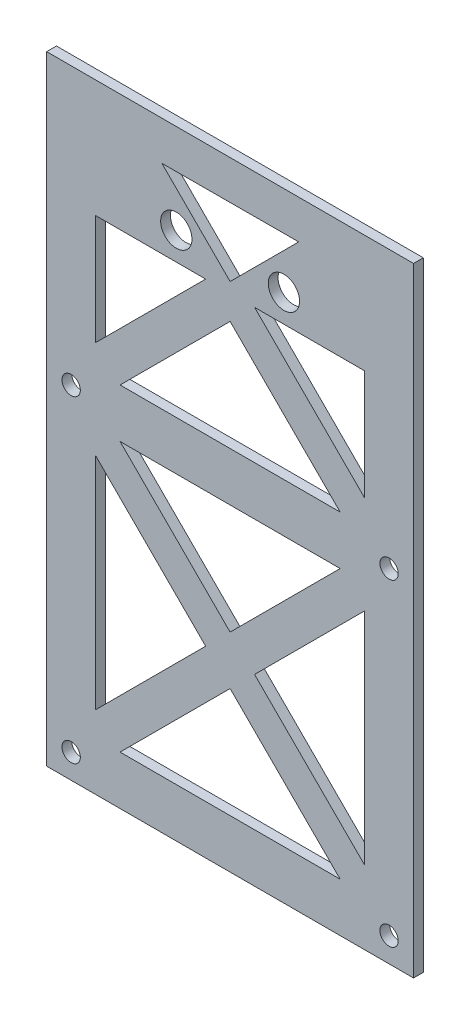
SolidWorks part; units mm, degrees
ref_plane "Front Plane" through (0, 0, 0) normal (0, 0, 1) x (1, 0, 0)
ref_plane "Top Plane" through (0, 0, 0) normal (0, 1, 0) x (1, 0, 0)
ref_plane "Right Plane" through (0, 0, 0) normal (1, 0, 0) x (0, 0, -1)
sketch "Sketch1" plane through (0, 0, 0) normal (0, 0, 1) x (1, 0, 0)
  line L2 (-37.5, -138.0294) -> (37.5, -138.0294)
  line L3 (5, -162.0484) -> (27.5, -162.0484)
  line L6 (-37.5, -264.5484) -> (37.5, -264.5484)
  line L7 (-27.5, -204.5484) -> (-27.5, -249.5484)
  line L8 (37.5, -264.5484) -> (37.5, -138.0294)
  line L9 (-37.5, -264.5484) -> (-37.5, -138.0294)
  line L11 (-22.5, -254.5484) -> (22.5, -254.5484)
  line L12 (27.5, -249.5484) -> (27.5, -204.5484)
  line L13 (-5, -162.0484) -> (-27.5, -162.0484)
  line L14 (-22.5, -199.5484) -> (22.5, -199.5484)
  line L15 (-27.5, -184.5484) -> (-27.5, -162.0484)
  line L17 (27.5, -184.5484) -> (27.5, -162.0484)
  line L19 (-27.5, -249.5484) -> (-5, -227.0484)
  line L20 (27.5, -204.5484) -> (5, -227.0484)
  line L21 (-27.5, -204.5484) -> (-5, -227.0484)
  line L22 (-22.5, -199.5484) -> (0, -222.0484)
  line L23 (0, -222.0484) -> (22.5, -199.5484)
  line L24 (0, -232.0484) -> (22.5, -254.5484)
  line L25 (5, -227.0484) -> (27.5, -249.5484)
  line L26 (-22.5, -189.5484) -> (22.5, -189.5484)
  line L27 (0, -232.0484) -> (-22.5, -254.5484)
  line L31 (-27.5, -184.5484) -> (-5, -162.0484)
  line L32 (0, -167.0484) -> (22.5, -189.5484)
  line L33 (5, -162.0484) -> (27.5, -184.5484)
  line L34 (0, -167.0484) -> (-22.5, -189.5484)
  line L35 (14.0243, -145.954) -> (0, -159.9784)
  line L37 (0, -159.9784) -> (-13.9583, -146.0201)
  line L38 (-13.9583, -146.0201) -> (14.0243, -145.954)
  circle A0 centre (32.5, -259.5484) radius 1.875
  circle A1 centre (-32.5, -259.5484) radius 1.875
  circle A2 centre (-32.5, -194.5484) radius 1.875
  circle A3 centre (32.5, -194.5484) radius 1.875
  circle A4 centre (11, -156.3894) radius 3.2
  circle A5 centre (-11, -156.3894) radius 3.2
  point P30 (0, -227.0484)
  dimension "D3" = 3.75
  dimension "D11" = 5
  dimension "D2" = 10
  dimension "D4" = 5
  dimension "D5" = 5
  dimension "D6" = 10
  dimension "D7" = 4
  dimension "D8" = 10
  dimension "D10" = 10
  dimension "D12" = 90
  dimension "D13" = 5
  dimension "D17" = 5
  dimension "D18" = 5
  dimension "D20" = 15
  dimension "D21" = 15
  dimension "D22" = 37.5
  dimension "D24" = 90
  dimension "D27" = 37.5
extrude "Boss-Extrude2" add sketch "Sketch1" along normal blind 2
